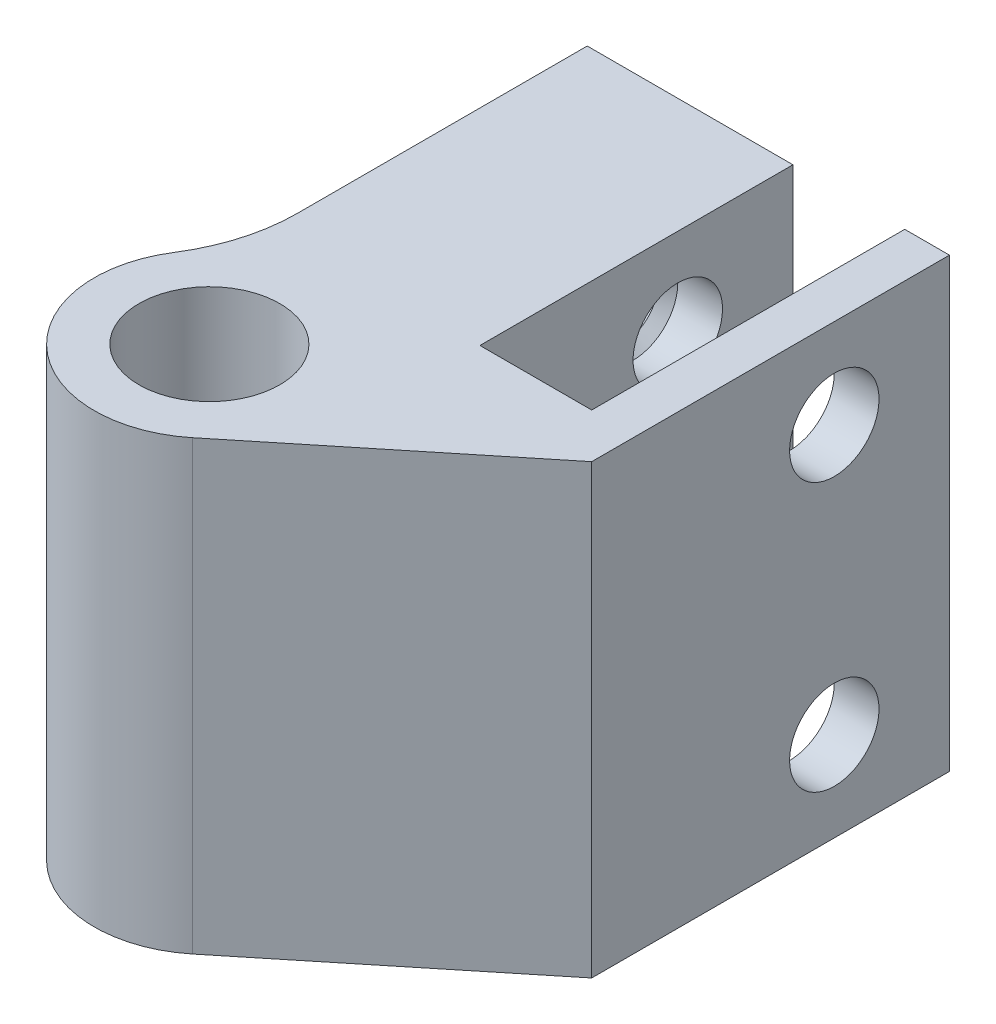
SolidWorks part; units mm, degrees
ref_plane "Front Plane" through (0, 0, 0) normal (0, 0, 1) x (1, 0, 0)
ref_plane "Top Plane" through (0, 0, 0) normal (0, 1, 0) x (1, 0, 0)
ref_plane "Right Plane" through (0, 0, 0) normal (1, 0, 0) x (0, 0, -1)
sketch "Sketch1" plane through (0, 0, 0) normal (0, 1, 0) x (1, 0, 0)
  line L0 (1.397, 7.62) -> (-1.397, 7.62)
  line L2 (-1.397, 7.62) -> (-1.397, 25.4)
  line L3 (-1.397, 25.4) -> (-3.937, 25.4)
  line L4 (-3.937, 8.9535) -> (-3.937, 25.4)
  line L6 (1.397, 7.62) -> (1.397, 25.4)
  line L7 (1.397, 25.4) -> (3.937, 25.4)
  line L8 (3.937, 8.9535) -> (3.937, 25.4)
  line L9 (-1.397, 25.4) -> (1.397, 25.4)
  line L10 (16.637, 5.08) -> (4.1214, -5.078)
  line L11 (1.397, 7.62) -> (16.637, 7.62)
  line L12 (1.397, 7.62) -> (1.397, 5.08)
  line L13 (1.397, 5.08) -> (16.637, 5.08)
  line L14 (16.637, 7.62) -> (16.637, 5.08)
  line L15 (14.097, 7.62) -> (16.637, 7.62)
  line L16 (14.097, 7.62) -> (14.097, 25.4)
  line L17 (14.097, 25.4) -> (16.637, 25.4)
  line L18 (16.637, 7.62) -> (16.637, 25.4)
  line L20 (3.937, 25.4) -> (7.747, 25.4)
  line L21 (3.937, 25.4) -> (3.937, 5.08)
  line L22 (3.937, 5.08) -> (7.747, 5.08)
  line L23 (7.747, 25.4) -> (7.747, 5.08)
  circle A0 centre (0, 0) radius 4
  arc A1 (-5.5206, 3.5063) -> (5.5206, 3.5063) centre (0, 0) ccw
  arc A2 (3.937, 8.9535) -> (5.5206, 3.5063) centre (14.097, 8.9535) ccw
  arc A3 (-3.937, 8.9535) -> (-5.5206, 3.5063) centre (-14.097, 8.9535) cw
  dimension "D1" = 8
  dimension "D2" = 2.54
  dimension "D3" = 2.794
  dimension "D10" = 10.16
  dimension "D4" = 1.397
  dimension "D5" = 2.54
  dimension "D6" = 2.54
  dimension "D7" = 25.4
  dimension "D8" = 25.4
  dimension "D9" = 7.62
  dimension "D11" = 2.54
  dimension "D12" = 10.16
  dimension "D13" = 12.7
  dimension "D14" = 25.4
  dimension "D15" = 3.81
extrude "Boss-Extrude1" add sketch "Sketch1" along normal blind 25.4 contours L11 A2 L13 L14 | A2 L11 L12 L13 | L4 A3 A1 A2 L13 L12 L0 L2 L3 A0 | L9 L2 L0 L6 | L11 L18 L17 L16 | L13 A2 A1 L10 | L21 L20 L23 L22 | L12 L11 L14 L13 | A1 A2 L8 L7 L6 L0 L2 L3 L4 A3 | A0 region at (-1.0408, 0, -5.8291) region at (0, 0, -16.51) region at (2.667, 0, -6.35) region at (12.192, 0, -6.35) region at (9.4962, 0, -2.302) region at (15.367, 0, -16.51)
sketch "Sketch2" plane through (3.937, 0, 0) normal (1, 0, 0) x (0, 0, -1)
  line L0 (8.9535, 25.4) -> (25.4, 25.4) construction
  line L1 (8.9535, 0) -> (25.4, 0) construction
  line L2 (8.9535, 25.4) -> (8.9535, 0) construction
  circle A0 centre (18.8595, 20.32) radius 2.54
  circle A1 centre (18.8595, 5.08) radius 2.54
  dimension "D1" = 5.08
  dimension "D2" = 5.08
  dimension "D3" = 5.08
  dimension "D4" = 5.08
  dimension "D5" = 9.906
  dimension "D6" = 9.906
extrude "Cut-Extrude1" cut sketch "Sketch2" along normal through all
sketch "Sketch4" plane through (3.937, 0, 0) normal (1, 0, 0) x (0, 0, -1)
  circle A0 centre (18.8595, 20.32) radius 1.9844
  circle A1 centre (18.8595, 5.08) radius 1.9844
  dimension "D1" = 3.9688
  dimension "D2" = 3.9688
extrude "Cut-Extrude3" cut sketch "Sketch4" against normal through all
chamfer "Chamfer1" distance 1.27 angle 45 2 edges at (3.937, 20.32, -21.3995) (3.937, 5.08, -21.3995)
